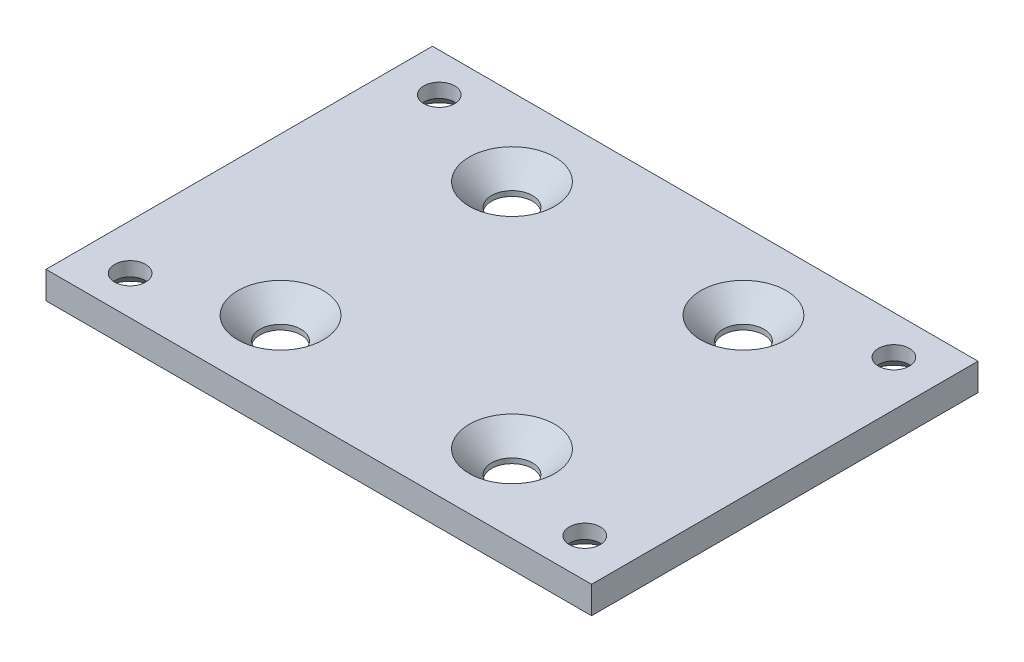
SolidWorks part; units mm, degrees
material "6061-T6 (SS)"
ref_plane "Front Plane" through (0, 0, 0) normal (0, 0, 1) x (1, 0, 0)
ref_plane "Top Plane" through (0, 0, 0) normal (0, 1, 0) x (1, 0, 0)
ref_plane "Right Plane" through (0, 0, 0) normal (1, 0, 0) x (0, 0, -1)
sketch "Base Plate" plane through (0, 0, 0) normal (0, 1, 0) x (1, 0, 0)
  line L9 (-30, -21.25) -> (30, -21.25)
  line L10 (-30, -21.25) -> (-30, 21.25)
  line L15 (-30, 21.25) -> (30, 21.25)
  line L16 (30, -21.25) -> (30, 21.25)
  line L17 (-30, -21.25) -> (30, 21.25) construction
  line L18 (-30, 21.25) -> (30, -21.25) construction
  point P0 (0, 0)
  dimension "D1" = 42.5
  dimension "D2" = 60
extrude "Boss-Extrude1" add sketch "Base Plate" along normal blind 3
hole_wizard "Motor Holes M4" positions "Sketch3" profile "Sketch4" countersink size "M4" standard "ANSI Metric" end condition through all
sketch "Sketch3" plane through (0, 3, 0) normal (0, 1, 0) x (1, 0, 0)
  line L0 (-12.7279, 12.7279) -> (0, 0) construction
  line L2 (-30, -21.25) -> (30, -21.25) construction
  circle A0 centre (0, 0) radius 18 construction
  point P5 (-12.7279, 12.7279)
  point P23 (12.7279, 12.7279)
  point P24 (12.7279, -12.7279)
  point P25 (-12.7279, -12.7279)
  dimension "D1" = 36
  dimension "D3" = 4
  dimension "D2" = 45
sketch "Sketch4" plane through (-12.7279, 3, 12.7279) normal (1, 0, 0) x (0, 0, 1)
  line L0 (0, 0) -> (0, 3)
  line L1 (0, 3) -> (2.25, 3)
  line L2 (2.25, 3) -> (2.25, 2.45)
  line L3 (2.25, 2.45) -> (4.7, 0)
  line L5 (4.7, 0) -> (0, 0)
  line L6 (-2.25, 2.45) -> (-4.7, 0) construction
  line L11 (0, -6.35) -> (0, 107.95) construction
  dimension "Thru Hole Dia." = 4.5
  dimension "Thru Hole Depth" = 3
  dimension "Near C'Sink Dia." = 9.4
  dimension "Near C'Sink Angle" = 90
hole_wizard "Clamp Holes M3" positions "Sketch5" profile "Sketch6" countersink size "M3" standard "ANSI Metric" end condition through all
sketch "Sketch5" plane through (0, 0, 0) normal (0, -1, 0) x (-1, 0, 0)
  line L1 (-25, -17) -> (25, -17)
  line L2 (-25, -17) -> (-25, 17)
  line L3 (-25, 17) -> (25, 17)
  line L4 (25, -17) -> (25, 17)
  line L5 (-25, -17) -> (25, 17) construction
  line L6 (-25, 17) -> (25, -17) construction
  point P2 (25, 17)
  point P5 (-25, -17)
  point P6 (-25, 17)
  point P7 (25, -17)
  point P189 (0, 0)
  point P190 (0, 0)
  point P191 (0, 17)
  point P193 (25, 0)
  dimension "D1" = 34
  dimension "D2" = 50
sketch "Sketch6" plane through (-25, 0, -17) normal (1, 0, 0) x (0, 0, -1)
  line L0 (0, 0) -> (0, 3)
  line L1 (0, 3) -> (1.7, 3)
  line L2 (1.7, 3) -> (1.7, 1.45)
  line L3 (1.7, 1.45) -> (3.15, 0)
  line L5 (3.15, 0) -> (0, 0)
  line L6 (-1.7, 1.45) -> (-3.15, 0) construction
  line L11 (0, -6.35) -> (0, 107.95) construction
  dimension "Thru Hole Dia." = 3.4
  dimension "Thru Hole Depth" = 3
  dimension "Near C'Sink Dia." = 6.3
  dimension "Near C'Sink Angle" = 90
